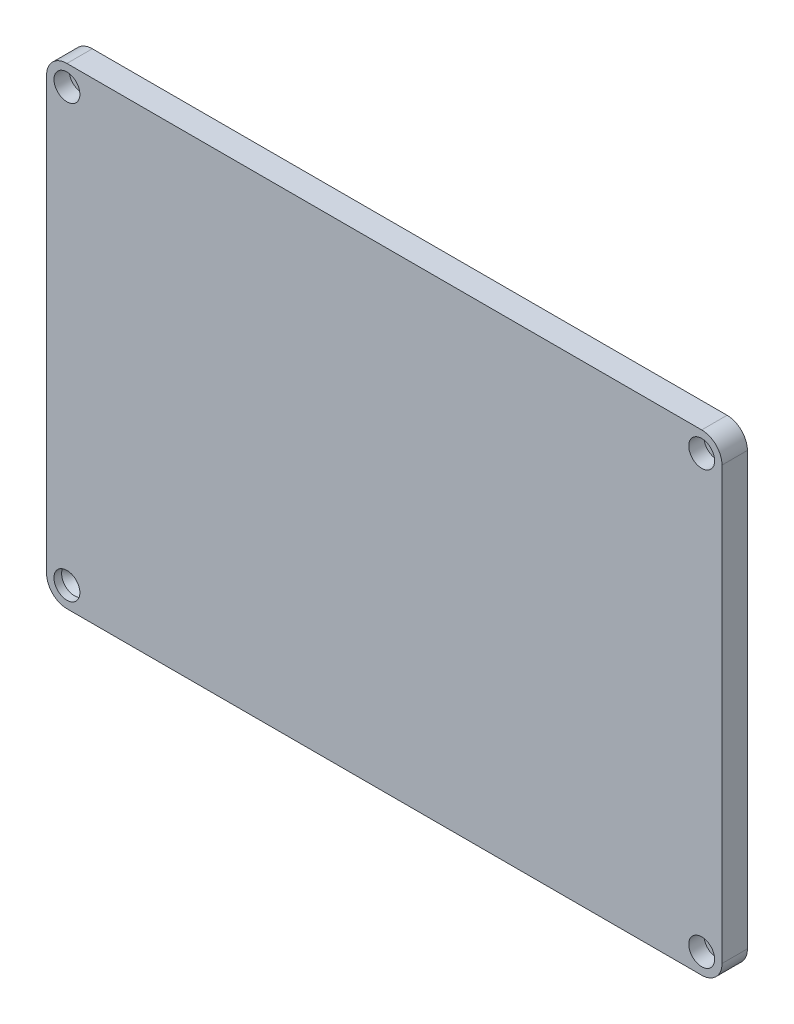
SolidWorks part; units mm, degrees
ref_plane "Front Plane" through (0, 0, 0) normal (0, 0, 1) x (1, 0, 0)
ref_plane "Top Plane" through (0, 0, 0) normal (0, 1, 0) x (1, 0, 0)
ref_plane "Right Plane" through (0, 0, 0) normal (1, 0, 0) x (0, 0, -1)
sketch "Sketch2" plane through (0, 0, 0) normal (0, 0, 1) x (1, 0, 0)
  line L8 (66.5, -42.5) -> (66.5, 42.5)
  line L9 (62.5, 46.5) -> (-62.5, 46.5)
  line L10 (-66.5, 42.5) -> (-66.5, -42.5)
  line L11 (-62.5, -46.5) -> (62.5, -46.5)
  line L12 (-62.5, -36.8431) -> (-62.5, 36.8431)
  line L13 (56.8431, -42.5) -> (-56.8431, -42.5)
  line L14 (-56.8431, 42.5) -> (56.8431, 42.5)
  line L15 (62.5, 36.8431) -> (62.5, -36.8431)
  circle A4 centre (-62.5, 42.5) radius 1.25
  circle A5 centre (62.5, 42.5) radius 1.25
  circle A6 centre (-62.5, -42.5) radius 1.25
  circle A7 centre (62.5, -42.5) radius 1.25
  arc A8 (62.5, -46.5) -> (66.5, -42.5) centre (62.5, -42.5) ccw
  arc A9 (66.5, 42.5) -> (62.5, 46.5) centre (62.5, 42.5) ccw
  arc A10 (-62.5, 46.5) -> (-66.5, 42.5) centre (-62.5, 42.5) ccw
  arc A11 (-66.5, -42.5) -> (-62.5, -46.5) centre (-62.5, -42.5) ccw
  arc A20 (-62.5, -36.8431) -> (-61.1667, -38.7288) centre (-60.5, -36.8431) ccw
  arc A21 (-58.7288, -41.1667) -> (-61.1667, -38.7288) centre (-62.5, -42.5) ccw
  arc A22 (-58.7288, -41.1667) -> (-56.8431, -42.5) centre (-56.8431, -40.5) ccw
  arc A23 (-61.1667, 38.7288) -> (-62.5, 36.8431) centre (-60.5, 36.8431) ccw
  arc A24 (-61.1667, 38.7288) -> (-58.7288, 41.1667) centre (-62.5, 42.5) ccw
  arc A25 (-56.8431, 42.5) -> (-58.7288, 41.1667) centre (-56.8431, 40.5) ccw
  arc A26 (58.7288, 41.1667) -> (56.8431, 42.5) centre (56.8431, 40.5) ccw
  arc A27 (58.7288, 41.1667) -> (61.1667, 38.7288) centre (62.5, 42.5) ccw
  arc A28 (62.5, 36.8431) -> (61.1667, 38.7288) centre (60.5, 36.8431) ccw
  arc A29 (61.1667, -38.7288) -> (62.5, -36.8431) centre (60.5, -36.8431) ccw
  arc A30 (61.1667, -38.7288) -> (58.7288, -41.1667) centre (62.5, -42.5) ccw
  arc A31 (56.8431, -42.5) -> (58.7288, -41.1667) centre (56.8431, -40.5) ccw
extrude "Boss-Extrude1" add sketch "Sketch2" along normal blind 2
sketch "Sketch3" plane through (0, 0, 2) normal (0, 0, 1) x (1, 0, 0)
  line L4 (66.5, -42.5) -> (66.5, 42.5)
  line L5 (62.5, 46.5) -> (-62.5, 46.5)
  line L6 (-66.5, 42.5) -> (-66.5, -42.5)
  line L7 (-62.5, -46.5) -> (62.5, -46.5)
  line L8 (66.5, -42.5) -> (66.5, 42.5)
  line L9 (62.5, 46.5) -> (-62.5, 46.5)
  line L10 (-66.5, 42.5) -> (-66.5, -42.5)
  line L11 (-62.5, -46.5) -> (62.5, -46.5)
  circle A0 centre (-62.5, 42.5) radius 2.55
  circle A1 centre (62.5, 42.5) radius 2.55
  circle A2 centre (62.5, -42.5) radius 2.55
  circle A3 centre (-62.5, -42.5) radius 2.55
  arc A4 (62.5, -46.5) -> (66.5, -42.5) centre (62.5, -42.5) ccw
  arc A5 (66.5, 42.5) -> (62.5, 46.5) centre (62.5, 42.5) ccw
  arc A6 (-62.5, 46.5) -> (-66.5, 42.5) centre (-62.5, 42.5) ccw
  arc A7 (-66.5, -42.5) -> (-62.5, -46.5) centre (-62.5, -42.5) ccw
  arc A8 (62.5, -46.5) -> (66.5, -42.5) centre (62.5, -42.5) ccw
  arc A9 (66.5, 42.5) -> (62.5, 46.5) centre (62.5, 42.5) ccw
  arc A10 (-62.5, 46.5) -> (-66.5, 42.5) centre (-62.5, 42.5) ccw
  arc A11 (-66.5, -42.5) -> (-62.5, -46.5) centre (-62.5, -42.5) ccw
  dimension "D1" = 0
extrude "Boss-Extrude2" add sketch "Sketch3" along normal blind 3
sketch "Sketch4" plane through (0, 0, 2) normal (0, 0, -1) x (-1, 0, 0)
  line L4 (62.5, -36.8431) -> (62.5, 36.8431)
  line L5 (56.8431, 42.5) -> (-56.8431, 42.5)
  line L6 (-62.5, 36.8431) -> (-62.5, -36.8431)
  line L7 (-56.8431, -42.5) -> (56.8431, -42.5)
  line L8 (62.5, -36.8431) -> (62.5, 36.8431)
  line L9 (56.8431, 42.5) -> (-56.8431, 42.5)
  line L10 (-62.5, 36.8431) -> (-62.5, -36.8431)
  line L11 (-56.8431, -42.5) -> (56.8431, -42.5)
  arc A12 (61.1667, -38.7288) -> (62.5, -36.8431) centre (60.5, -36.8431) ccw
  arc A13 (62.5, 36.8431) -> (61.1667, 38.7288) centre (60.5, 36.8431) ccw
  arc A14 (58.7288, 41.1667) -> (61.1667, 38.7288) centre (62.5, 42.5) ccw
  arc A15 (58.7288, 41.1667) -> (56.8431, 42.5) centre (56.8431, 40.5) ccw
  arc A16 (-56.8431, 42.5) -> (-58.7288, 41.1667) centre (-56.8431, 40.5) ccw
  arc A17 (-61.1667, 38.7288) -> (-58.7288, 41.1667) centre (-62.5, 42.5) ccw
  arc A18 (-61.1667, 38.7288) -> (-62.5, 36.8431) centre (-60.5, 36.8431) ccw
  arc A19 (-62.5, -36.8431) -> (-61.1667, -38.7288) centre (-60.5, -36.8431) ccw
  arc A20 (-58.7288, -41.1667) -> (-61.1667, -38.7288) centre (-62.5, -42.5) ccw
  arc A21 (-58.7288, -41.1667) -> (-56.8431, -42.5) centre (-56.8431, -40.5) ccw
  arc A22 (56.8431, -42.5) -> (58.7288, -41.1667) centre (56.8431, -40.5) ccw
  arc A23 (61.1667, -38.7288) -> (58.7288, -41.1667) centre (62.5, -42.5) ccw
  arc A24 (61.1667, -38.7288) -> (62.5, -36.8431) centre (60.5, -36.8431) ccw
  arc A25 (62.5, 36.8431) -> (61.1667, 38.7288) centre (60.5, 36.8431) ccw
  arc A26 (58.7288, 41.1667) -> (61.1667, 38.7288) centre (62.5, 42.5) ccw
  arc A27 (58.7288, 41.1667) -> (56.8431, 42.5) centre (56.8431, 40.5) ccw
  arc A28 (-56.8431, 42.5) -> (-58.7288, 41.1667) centre (-56.8431, 40.5) ccw
  arc A29 (-61.1667, 38.7288) -> (-58.7288, 41.1667) centre (-62.5, 42.5) ccw
  arc A30 (-61.1667, 38.7288) -> (-62.5, 36.8431) centre (-60.5, 36.8431) ccw
  arc A31 (-62.5, -36.8431) -> (-61.1667, -38.7288) centre (-60.5, -36.8431) ccw
  arc A32 (-58.7288, -41.1667) -> (-61.1667, -38.7288) centre (-62.5, -42.5) ccw
  arc A33 (-58.7288, -41.1667) -> (-56.8431, -42.5) centre (-56.8431, -40.5) ccw
  arc A34 (56.8431, -42.5) -> (58.7288, -41.1667) centre (56.8431, -40.5) ccw
  arc A35 (61.1667, -38.7288) -> (58.7288, -41.1667) centre (62.5, -42.5) ccw
  dimension "D1" = 0
extrude "Boss-Extrude3" add sketch "Sketch4" along normal blind 3
chamfer "Chamfer1" distance 0.5 angle 45 16 edges at (-57.9978, -42.133, -1) (-59.6716, -39.6716, -1) (0, -42.5, -1) (-62.133, -37.9978, -1) (57.9978, -42.133, -1) (-62.5, 0, -1) (59.6716, -39.6716, -1) (-62.133, 37.9978, -1) (62.133, -37.9978, -1) (-59.6716, 39.6716, -1) (62.5, 0, -1) (-57.9978, 42.133, -1) (62.133, 37.9978, -1) (59.6716, 39.6716, -1) (57.9978, 42.133, -1) (0, 42.5, -1)
chamfer "Chamfer2" distance 1.5 angle 45 1 edges at (-59.95, -42.5, 2)
